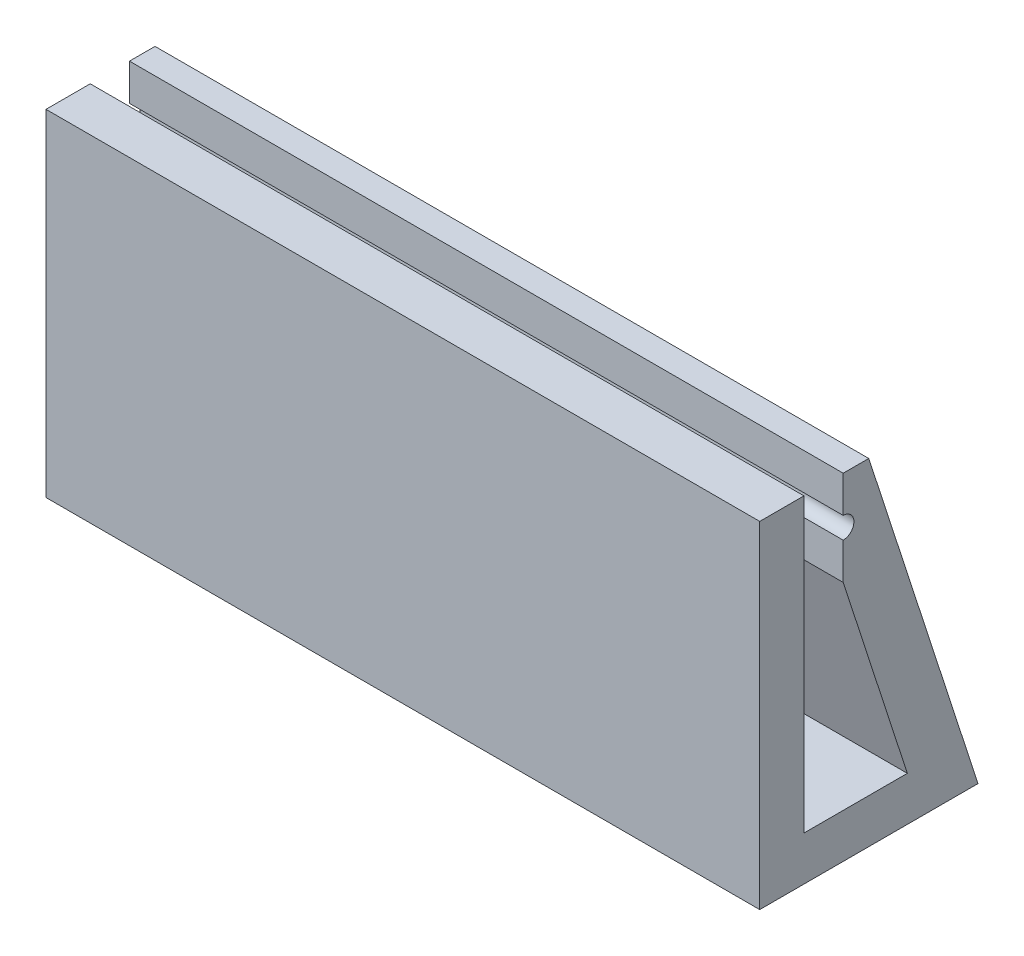
SolidWorks part; units mm, degrees
ref_plane "Front Plane" through (0, 0, 0) normal (0, 0, 1) x (1, 0, 0)
ref_plane "Top Plane" through (0, 0, 0) normal (0, 1, 0) x (1, 0, 0)
ref_plane "Right Plane" through (0, 0, 0) normal (1, 0, 0) x (0, 0, -1)
sketch "Sketch1" plane through (0, 0, 0) normal (1, 0, 0) x (0, 0, -1)
  line L0 (0, 0) -> (6.1164, 0)
  line L1 (0, 5.3304) -> (1.2392, 5.3304) construction
  line L2 (2.3392, 9.4216) -> (2.3392, 6.771) construction
  line L3 (2.3392, 6.771) -> (4.1366, 1.2392)
  line L4 (4.1366, 1.2392) -> (1.2392, 1.2392)
  line L5 (1.2392, 1.2392) -> (1.2392, 9.4216)
  line L6 (1.2392, 9.4216) -> (0, 9.4216)
  line L7 (0, 9.4216) -> (0, 0)
  line L8 (2.3392, 9.4216) -> (2.3392, 8.3963)
  line L9 (2.3392, 7.7963) -> (2.3392, 6.771)
  line L10 (2.3392, 9.4216) -> (3.0551, 9.4216)
  line L11 (3.0551, 9.4216) -> (6.1164, 0)
  line L12 (2.6879, 1.2392) -> (2.6879, 0) construction
  arc A0 (2.3392, 8.3963) -> (2.3392, 7.7963) centre (2.3392, 8.0963) cw
  dimension "D1" = 0.3
  dimension "D2" = 1.1
  dimension "D3" = 72
  dimension "D4" = 1.5
extrude "Boss-Extrude1" add sketch "Sketch1" along normal mid plane 20 contours L8 A0 L9 L3 L4 L5 L6 L7 L0 L11 L10
